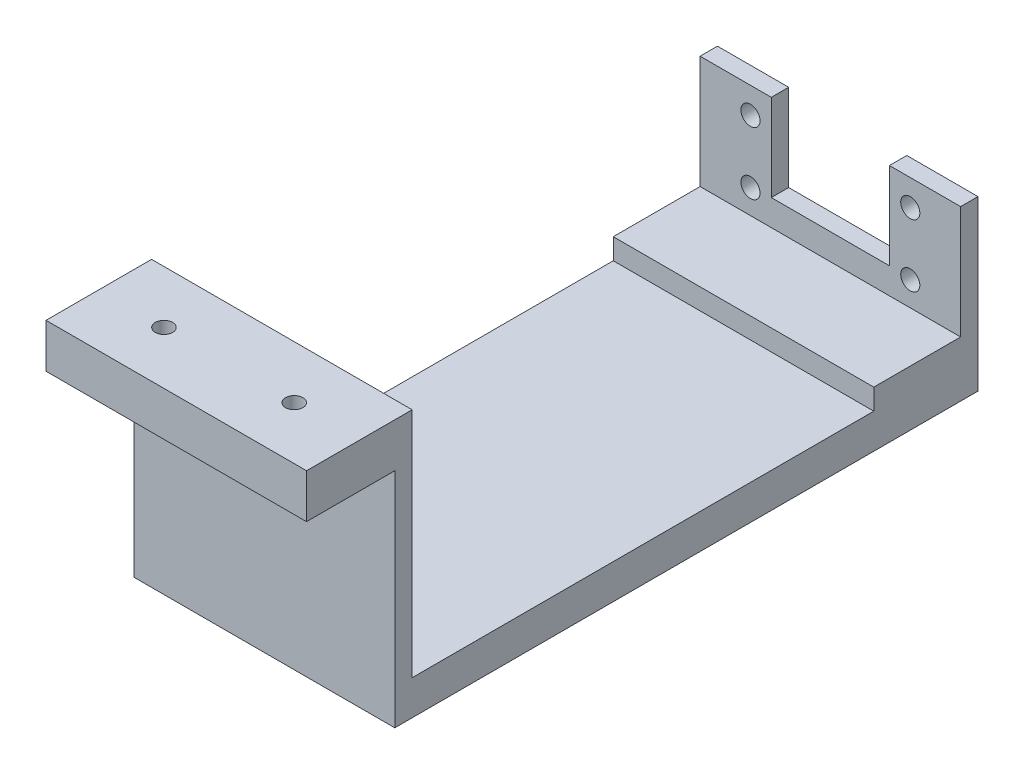
SolidWorks part; units mm, degrees
material "ABS"
ref_plane "Front Plane" through (0, 0, 0) normal (0, 0, 1) x (1, 0, 0)
ref_plane "Top Plane" through (0, 0, 0) normal (0, 1, 0) x (1, 0, 0)
ref_plane "Right Plane" through (0, 0, 0) normal (1, 0, 0) x (0, 0, -1)
sketch "Sketch1" plane through (0, 0, 0) normal (0, 0, 1) x (1, 0, 0)
  line L0 (20.5, 32.5) -> (20.5, 7.5)
  line L1 (0, 0) -> (75, 0)
  line L2 (0, 0) -> (0, 32.5)
  line L3 (0, 32.5) -> (75, 32.5)
  line L4 (75, 0) -> (75, 32.5)
  line L5 (20.5, 7.5) -> (54.5, 7.5)
  line L6 (54.5, 7.5) -> (54.5, 32.5)
  line L7 (37.5, 32.5) -> (37.5, 0) construction
  circle A0 centre (14.5, 25) radius 2.75
  circle A1 centre (14.5, 7) radius 2.75
  circle A2 centre (60.5, 7) radius 2.75
  circle A3 centre (60.5, 25) radius 2.75
  dimension "D6" = 5.5
  dimension "D7" = 46
  dimension "D8" = 34
  dimension "D1" = 32.5
  dimension "D2" = 75
  dimension "D3" = 17
  dimension "D4" = 18
  dimension "D5" = 25
  dimension "D9" = 25
  dimension "D10" = 14.5
  dimension "D11" = 6
extrude "Boss-Extrude1" add sketch "Sketch1" along normal blind 5 contours L7 L5 L0 L3 L2 L1 A1 A0 | L5 L7 L1 L4 L3 L6 A3 A2 region at (13.183, 14.1302, 0) region at (61.817, 14.1302, 0)
sketch "Sketch2" plane through (0, 0, 5) normal (0, 0, 1) x (1, 0, 0)
  line L0 (75, 0) -> (75, 32.5) construction
  line L1 (0, 0) -> (75, 0)
  line L2 (0, 0) -> (0, -6)
  line L3 (0, -6) -> (75, -6)
  line L4 (75, 0) -> (75, -6)
  dimension "D1" = 6
extrude "Boss-Extrude2" add sketch "Sketch2" along normal blind 25 and the other way blind 5
sketch "Sketch3" plane through (0, 0, 0) normal (0, 0, -1) x (-1, 0, 0)
  line L0 (0, -6) -> (0, 32.5) construction
  line L1 (-75, -6) -> (0, -6)
  line L2 (-75, -6) -> (-75, -16)
  line L3 (-75, -16) -> (0, -16)
  line L4 (0, -6) -> (0, -16)
  dimension "D1" = 10
extrude "Boss-Extrude3" add sketch "Sketch3" against normal blind 167.8942
sketch "Sketch4" plane through (0, -6, 0) normal (0, 1, 0) x (1, 0, 0)
  line L0 (75, -167.8942) -> (75, -30) construction
  line L1 (0, -167.8942) -> (75, -167.8942)
  line L2 (0, -167.8942) -> (0, -162.8942)
  line L3 (0, -162.8942) -> (75, -162.8942)
  line L4 (75, -167.8942) -> (75, -162.8942)
  dimension "D1" = 5
extrude "Boss-Extrude4" add sketch "Sketch4" along normal blind 66.8
sketch "Sketch5" plane through (0, 0, 167.8942) normal (0, 0, 1) x (1, 0, 0)
  line L0 (0, -16) -> (0, 60.8) construction
  line L1 (0, 48.1) -> (75, 48.1)
  line L2 (0, 48.1) -> (0, 60.8)
  line L3 (0, 60.8) -> (75, 60.8)
  line L4 (75, 48.1) -> (75, 60.8)
  line L5 (75, 60.8) -> (75, -16) construction
  line L6 (0, 60.8) -> (75, 60.8) construction
  dimension "D2" = 12.7
extrude "Boss-Extrude5" add sketch "Sketch5" along normal blind 25.4
sketch "Sketch6" plane through (0, 60.8, 0) normal (0, 1, 0) x (1, 0, 0)
  line L0 (0, -178.0942) -> (37.5, -178.0942) construction
  line L1 (37.5, -193.2942) -> (37.5, -162.8942) construction
  line L2 (75, -178.0942) -> (37.5, -178.0942) construction
  line L5 (0, -162.8942) -> (0, -193.2942)
  line L6 (0, -193.2942) -> (75, -193.2942)
  line L7 (75, -193.2942) -> (75, -162.8942)
  line L9 (0, -162.8942) -> (0, -193.2942)
  line L10 (0, -193.2942) -> (75, -193.2942)
  line L11 (75, -193.2942) -> (75, -162.8942)
  line L40 (75, -162.8942) -> (0, -162.8942)
  line L41 (75, -162.8942) -> (0, -162.8942)
  point P4 (18.75, -178.0942)
  point P10 (56.25, -178.0942)
  dimension "D1" = 0
hole_wizard "M5x0.8 Tapped Hole1" positions "Sketch6" profile "Sketch7" tap size "M5x0.8" standard "ANSI Metric" end condition through all
sketch "Sketch7" plane through (56.25, 60.8, 178.0942) normal (1, 0, 0) x (0, 0, 1)
  line L0 (0, 0) -> (0, 76.8)
  line L1 (0, 76.8) -> (2.5, 76.8)
  line L2 (2.5, 76.8) -> (2.5, 0)
  line L5 (2.5, 0) -> (0, 0)
  line L11 (0, -6.35) -> (0, 107.95) construction
  dimension "Thread Major Dia." = 5
  dimension "Thru Tap Drill Depth" = 76.8
